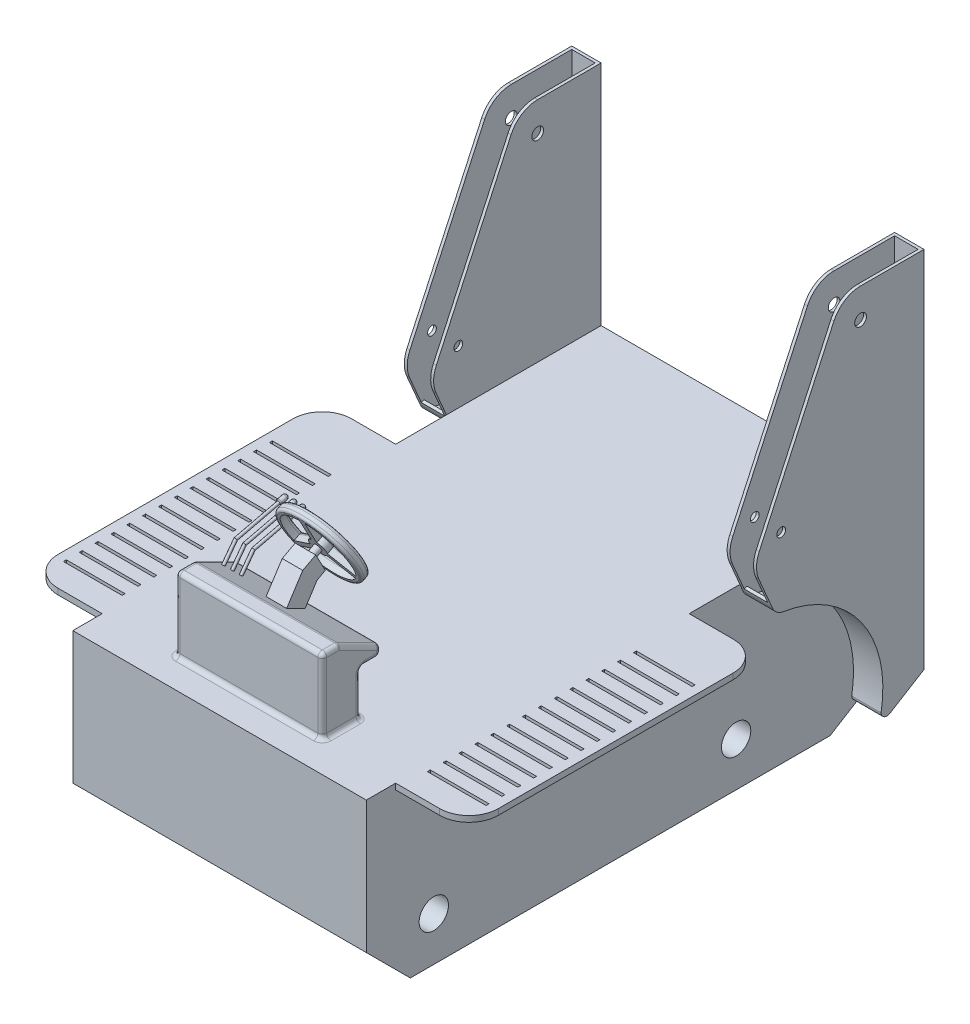
SolidWorks part; units mm, degrees
ref_plane "Front Plane" through (0, 0, 0) normal (0, 0, 1) x (1, 0, 0)
ref_plane "Top Plane" through (0, 0, 0) normal (0, 1, 0) x (1, 0, 0)
ref_plane "Right Plane" through (0, 0, 0) normal (1, 0, 0) x (0, 0, -1)
sketch "Sketch1" plane through (0, 0, 0) normal (1, 0, 0) x (0, 0, -1)
  line L0 (-865, 600) -> (935, 600)
  line L1 (935, 600) -> (935, 135)
  line L2 (935, 135) -> (715, 0)
  line L3 (715, 0) -> (-715, 0)
  line L4 (-715, 0) -> (-865, 150)
  line L5 (-865, 150) -> (-865, 600)
  circle A0 centre (-635, 150) radius 50
  circle A1 centre (395, 150) radius 50
  dimension "D7" = 100
  dimension "D1" = 1800
  dimension "D2" = 220
  dimension "D3" = 600
  dimension "D4" = 150
  dimension "D5" = 150
  dimension "D6" = 135
  dimension "D8" = 1030
  dimension "D9" = 150
  dimension "D10" = 540
extrude "Boss-Extrude1" add sketch "Sketch1" along normal mid plane 1000
sketch "Sketch2" plane through (500, 0, 0) normal (1, 0, 0) x (0, 0, -1)
  line L0 (935, 135) -> (935, 1375)
  line L1 (935, 1375) -> (719.0464, 1375)
  line L2 (628.213, 1316.8244) -> (373.5875, 763.8338)
  line L3 (372.5065, 682.6174) -> (418.6781, 574.8835)
  line L4 (935, 135) -> (819.3743, 64.0479)
  line L6 (715, 0) -> (935, 135) construction
  arc A0 (819.3743, 64.0479) -> (788.9218, 80.5336) centre (808.914, 81.0943) cw
  arc A1 (456.8981, 545.1818) -> (788.9218, 80.5336) centre (395, 150) cw
  circle A2 centre (395, 150) radius 50 construction
  arc A3 (719.0464, 1375) -> (628.213, 1316.8244) centre (719.0464, 1275) ccw
  arc A4 (373.5875, 763.8338) -> (372.5065, 682.6174) centre (464.421, 722.0093) ccw
  arc A5 (418.6781, 574.8835) -> (456.8981, 545.1818) centre (464.6354, 594.5795) ccw
  point P16 (655, 1375)
  point P19 (355, 723.4658)
  point P22 (430, 548.4658)
  dimension "D5" = 400
  dimension "D6" = 20
  dimension "D8" = 100
  dimension "D9" = 100
  dimension "D10" = 50
  dimension "D1" = 1240
  dimension "D2" = 280
  dimension "D3" = 75
  dimension "D4" = 175
  dimension "D7" = 35
extrude "Boss-Extrude2" add sketch "Sketch2" along normal blind 10 separate body
sketch "Sketch3" plane through (510, 0, 0) normal (1, 0, 0) x (0, 0, -1)
  line L0 (935, 135) -> (935, 1375) construction
  line L1 (935, 135) -> (935, 1375)
  line L2 (819.3743, 64.0479) -> (935, 135) construction
  line L3 (819.3743, 64.0479) -> (935, 135)
  line L4 (418.6781, 574.8835) -> (412.6282, 589)
  line L5 (372.5065, 682.6174) -> (418.6781, 574.8835) construction
  line L6 (427.8696, 578.8227) -> (421.8197, 592.9392)
  line L7 (814.1441, 72.5711) -> (925, 140.5963)
  line L8 (925, 140.5963) -> (925, 1375)
  line L9 (418.6781, 574.8835) -> (411.9336, 590.6207) construction
  line L10 (427.8696, 578.8227) -> (421.1251, 594.5599) construction
  line L12 (925, 1375) -> (935, 1375)
  line L13 (412.6282, 589) -> (421.8197, 592.9392)
  line L14 (935, 600) -> (-865, 600) construction
  arc A0 (788.9218, 80.5336) -> (819.3743, 64.0479) centre (808.914, 81.0943) ccw construction
  arc A1 (788.9218, 80.5336) -> (819.3743, 64.0479) centre (808.914, 81.0943) ccw
  arc A2 (788.9218, 80.5336) -> (456.8981, 545.1818) centre (395, 150) ccw construction
  arc A3 (788.9218, 80.5336) -> (456.8981, 545.1818) centre (395, 150) ccw
  arc A4 (418.6781, 574.8835) -> (456.8981, 545.1818) centre (464.6354, 594.5795) ccw construction
  arc A5 (418.6781, 574.8835) -> (456.8981, 545.1818) centre (464.6354, 594.5795) ccw
  arc A6 (427.8696, 578.8227) -> (458.4456, 555.0613) centre (464.6354, 594.5795) ccw
  arc A7 (798.9764, 79.9784) -> (458.4456, 555.0613) centre (395, 150) ccw
  arc A8 (798.9764, 79.9784) -> (814.1441, 72.5711) centre (808.914, 81.0943) ccw
  dimension "D2" = 11
  dimension "D1" = 10
extrude "Boss-Extrude3" add sketch "Sketch3" along normal blind 80
extrude "Boss-Extrude4" add sketch "Sketch2<3>" along normal blind 10 from offset 90
sketch "Sketch2<3>" plane through (500, 0, 0) normal (1, 0, 0) x (0, 0, -1) same geometry as "Sketch2"
mirror "Mirror1" about plane through (0, 0, 0) normal (1, 0, 0) of bodies 104
sketch "Sketch4" plane through (600, 0, 0) normal (1, 0, 0) x (0, 0, -1)
  line L0 (628.213, 1316.8244) -> (373.5875, 763.8338) construction
  circle A0 centre (719.0464, 1275) radius 20
  circle A1 centre (448.6243, 783.3403) radius 15
  arc A2 (373.5875, 763.8338) -> (372.5065, 682.6174) centre (464.421, 722.0093) ccw construction
  point P10 (364.4298, 723.3403)
  dimension "D1" = 30
  dimension "D4" = 40
  dimension "D2" = 60
  dimension "D3" = 60
extrude "Cut-Extrude1" cut sketch "Sketch4" against normal through all
sketch "Sketch5" plane through (0, 600, 0) normal (0, 1, 0) x (1, 0, 0)
  line L0 (0, 0) -> (0, -865) construction
  line L1 (500, -865) -> (-500, -865) construction
  line L2 (500, 935) -> (500, -865) construction
  line L3 (500, 235) -> (650, 235)
  line L4 (500, 235) -> (500, -765)
  line L5 (500, -765) -> (650, -765)
  line L6 (750, 135) -> (750, -665)
  line L7 (-750, 135) -> (-750, -665)
  line L8 (-500, -765) -> (-650, -765)
  line L9 (-500, 235) -> (-500, -765)
  line L10 (-500, 235) -> (-650, 235)
  arc A0 (650, 235) -> (750, 135) centre (650, 135) cw
  arc A1 (650, -765) -> (750, -665) centre (650, -665) ccw
  arc A2 (-650, -765) -> (-750, -665) centre (-650, -665) cw
  arc A3 (-650, 235) -> (-750, 135) centre (-650, 135) ccw
  point P13 (750, 235)
  point P16 (750, -765)
  point P25 (-750, -765)
  point P26 (-750, 235)
  dimension "D4" = 100
  dimension "D1" = 1000
  dimension "D2" = 250
  dimension "D3" = 100
extrude "Boss-Extrude5" add sketch "Sketch5" against normal blind 20
sketch "Sketch6" plane through (0, 600, 0) normal (0, 1, 0) x (1, 0, 0)
  line L0 (750, -665) -> (750, 135) construction
  line L1 (520, 35) -> (720, 35)
  line L2 (520, 35) -> (520, 25)
  line L3 (520, 25) -> (720, 25)
  line L4 (720, 35) -> (720, 25)
  line L5 (650, 235) -> (500, 235) construction
  line L6 (0, 0) -> (0, -449.5) construction
  line L7 (-720, 35) -> (-720, 25)
  line L8 (-520, 25) -> (-720, 25)
  line L9 (-520, 35) -> (-520, 25)
  line L10 (-520, 35) -> (-720, 35)
  dimension "D1" = 200
  dimension "D2" = 30
  dimension "D3" = 10
  dimension "D4" = 200
extrude "Cut-Extrude2" cut sketch "Sketch6" against normal through all
pattern_linear "LPattern1" count 14 spacing 54 along (0, 0, 1) of "Cut-Extrude2"
sketch "Sketch7" plane through (0, 600, 0) normal (0, 1, 0) x (1, 0, 0)
  line L0 (500, -865) -> (-500, -865) construction
  line L6 (-250, -565) -> (250, -565)
  line L7 (-250, -565) -> (-250, -765)
  line L8 (-250, -765) -> (250, -765)
  line L9 (250, -565) -> (250, -765)
  line L10 (-250, -565) -> (250, -765) construction
  line L11 (-250, -765) -> (250, -565) construction
  point P0 (0, -665)
  dimension "D1" = 500
  dimension "D2" = 100
  dimension "D3" = 200
extrude "Boss-Extrude6" add sketch "Sketch7" along normal blind 253
sketch "Sketch8" plane through (250, 0, 0) normal (1, 0, 0) x (0, 0, -1)
  line L0 (-705, 853) -> (-565, 853)
  line L1 (-765, 853) -> (-565, 853) construction
  line L2 (-565, 853) -> (-565, 783)
  line L3 (-565, 853) -> (-565, 600) construction
  line L4 (-565, 783) -> (-705, 853)
  line L5 (-565, 750) -> (-565, 600)
  line L6 (-565, 600) -> (-635, 600)
  line L7 (-765, 600) -> (-565, 600) construction
  line L8 (-635, 600) -> (-635, 750)
  line L9 (-635, 750) -> (-565, 750)
  dimension "D1" = 70
  dimension "D2" = 150
  dimension "D3" = 140
  dimension "D4" = 70
extrude "Cut-Extrude3" cut sketch "Sketch8" against normal through all
fillet "Fillet1" radius 15 21 edges at (0, 600, 635) (0, 750, 635) (0, 750, 565) (-250, 600, 700) (-250, 675, 635) (-250, 750, 600) (-250, 766.5, 565) (-250, 818, 635) (0, 783, 565) (250, 750, 600) (250, 675, 635) (250, 600, 700) (250, 818, 635) (250, 766.5, 565) (-250, 726.5, 765) (250, 726.5, 765) (0, 600, 765) (250, 853, 735) (0, 853, 765) (-250, 853, 735) (0, 853, 705)
ref_plane "Plane1" through (-220, 0, 0) normal (-1, 0, 0) x (0, 0, 1)
sketch "Sketch9" plane through (-220, 0, 0) normal (-1, 0, 0) x (0, 0, 1)
  line L0 (631.5477, 816.2738) -> (589.8462, 872.4965)
  line L1 (573.2918, 787.1459) -> (701.8328, 851.4164) construction
  line L2 (589.8462, 872.4965) -> (443.9511, 907.3477)
  dimension "D1" = 100
  dimension "D2" = 140
  dimension "D3" = 150
  dimension "D4" = 70
  dimension "D5" = 80
ref_plane "Plane2" through (-220, 907.3477, 443.9511) normal (0, 0.2323, -0.9726) x (-1, 0, 0)
sketch "Sketch10" plane through (-220, 907.3477, 443.9511) normal (0, 0.2323, -0.9726) x (-1, 0, 0)
  circle A0 centre (0, 0) radius 5
  dimension "D1" = 10
sweep "Sweep1" add profiles "Sketch10" path "Sketch9"
sketch "Sketch11" plane through (0, -51.3446, 214.9403) normal (0, 0.2323, -0.9726) x (-1, 0, 0)
  circle A0 centre (220, 985.6657) radius 8.5
  dimension "D1" = 17
extrude "Boss-Extrude7" add sketch "Sketch11" along normal blind 30
fillet "Fillet2" radius 8.5 1 edges at (-220, 922.5853, 416.7469)
fillet "Fillet3" radius 3.5 1 edges at (-220, 915.6151, 445.926)
pattern_linear "LPattern2" count 3 spacing 30 along (1, 0, 0) of bodies 114
sketch "Sketch12" plane through (0, 0, 0) normal (1, 0, 0) x (0, 0, -1)
  line L0 (-671.4223, 836.2111) -> (-616.4983, 920.9717)
  line L1 (-701.8328, 851.4164) -> (-573.2918, 787.1459) construction
  line L2 (-616.4983, 920.9717) -> (-572.3744, 944.4894)
  line L3 (-572.3744, 944.4894) -> (-539.4497, 882.7159)
  line L4 (-539.4497, 882.7159) -> (-567.5979, 867.7131)
  line L5 (-567.5979, 867.7131) -> (-608.4225, 804.7112)
  line L6 (-671.4223, 836.2111) -> (-608.4225, 804.7112)
  dimension "D1" = 101
  dimension "D2" = 151
  dimension "D3" = 50
  dimension "D4" = 70
  dimension "D5" = 34
  dimension "D6" = 70
extrude "Boss-Extrude8" add sketch "Sketch12" along normal mid plane 70
sketch "Sketch13" plane through (0, -28.6281, 53.7122) normal (0, 0.4704, -0.8825) x (-1, 0, 0)
  line L0 (-35, 1102.7094) -> (35, 1102.7094) construction
  line L1 (35, 1032.7094) -> (35, 1102.7094) construction
  circle A0 centre (0, 1067.7094) radius 12.5
  dimension "D1" = 25
  dimension "D2" = 35
  dimension "D3" = 35
extrude "Boss-Extrude9" add sketch "Sketch13" along normal blind 30
sketch "Sketch14" plane through (0, -14.5175, 27.2379) normal (0, 0.4704, -0.8825) x (-1, 0, 0)
  line L2 (-9, 1184.3627) -> (-9, 1096.3276)
  line L3 (9, 1184.3627) -> (9, 1096.3276)
  line L4 (105.5247, 1017.177) -> (29.2841, 1061.1945)
  line L5 (96.5247, 1001.5885) -> (20.2841, 1045.6061)
  line L6 (-96.5247, 1001.5885) -> (-20.2841, 1045.6061)
  line L7 (-105.5247, 1017.177) -> (-29.2841, 1061.1945)
  arc A0 (-9, 1096.3276) -> (-29.2841, 1061.1945) centre (0, 1067.7094) ccw
  circle A1 centre (0, 1067.7094) radius 135
  arc A2 (105.5247, 1017.177) -> (9, 1184.3627) centre (0, 1067.7094) ccw
  arc A5 (29.2841, 1061.1945) -> (9, 1096.3276) centre (0, 1067.7094) ccw
  arc A6 (-20.2841, 1045.6061) -> (20.2841, 1045.6061) centre (0, 1067.7094) ccw
  arc A7 (-96.5247, 1001.5885) -> (96.5247, 1001.5885) centre (0, 1067.7094) ccw
  arc A8 (-9, 1184.3627) -> (-105.5247, 1017.177) centre (0, 1067.7094) ccw
  circle A9 centre (0, 1067.7094) radius 12.5 construction
  point P21 (0, 1067.7094)
  dimension "D1" = 270
  dimension "D2" = 18
  dimension "D3" = 60
  dimension "D4" = 18
  dimension "D5" = 3
extrude "Boss-Extrude10" add sketch "Sketch14" along normal blind 30
fillet "Fillet4" radius 9 14 edges at (25.9808, 955.0609, 510.0186) (9, 1005.9233, 537.1277) (101.325, 993.4488, 530.479) (67.4044, 916.6523, 489.5472) (0, 915.3494, 488.8528) (58.4044, 902.8958, 482.2151) (0, 838.5738, 447.9321) (-58.4044, 902.8958, 482.2151) (-101.325, 993.4488, 530.479) (-9, 1005.9233, 537.1277) (-25.9808, 955.0609, 510.0186) (-67.4044, 916.6523, 489.5472) (0, 1060.9584, 566.4609) (0, 1046.8478, 592.9353)
